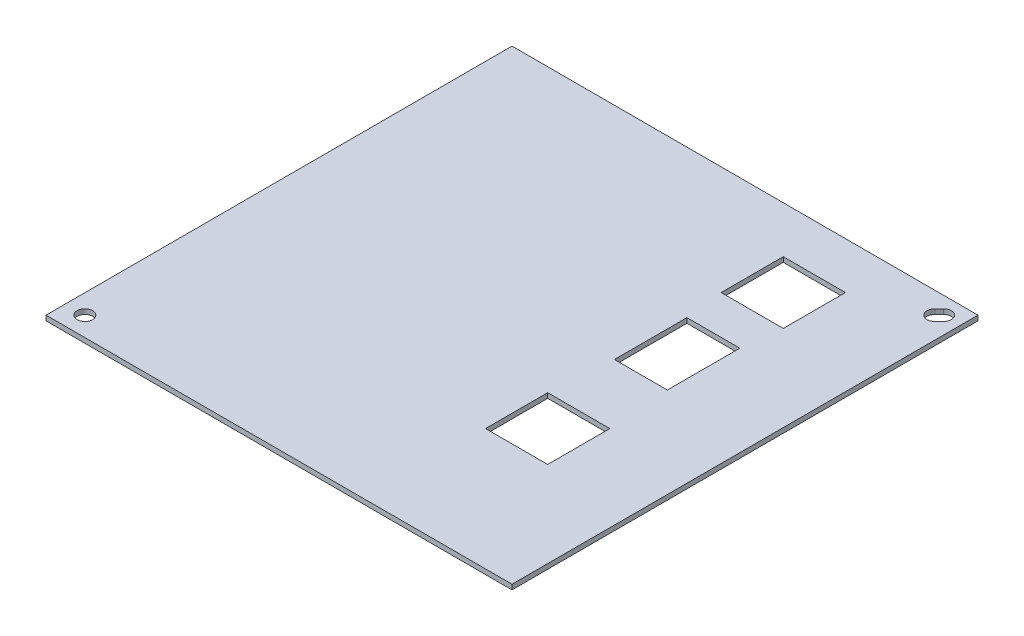
SolidWorks part; units mm, degrees
material "Acrylic (Medium-high impact)"
ref_plane "Front Plane" through (0, 0, 0) normal (0, 0, 1) x (1, 0, 0)
ref_plane "Top Plane" through (0, 0, 0) normal (0, 1, 0) x (1, 0, 0)
ref_plane "Right Plane" through (0, 0, 0) normal (1, 0, 0) x (0, 0, -1)
sketch "Sketch1" plane through (0, 0, 0) normal (0, 1, 0) x (1, 0, 0)
  line L1 (-150, -150) -> (150, -150)
  line L2 (-150, -150) -> (-150, 150)
  line L3 (-150, 150) -> (150, 150)
  line L4 (150, -150) -> (150, 150)
  line L5 (-150, -150) -> (150, 150) construction
  line L6 (-150, 150) -> (150, -150) construction
  point P0 (0, 0)
  dimension "D1" = 300
  dimension "D2" = 300
extrude "Boss-Extrude1" add sketch "Sketch1" along normal blind 3.175
sketch "Sketch2" plane through (0, 3.175, 0) normal (0, 1, 0) x (1, 0, 0)
  line L0 (138.9142, 138.9142) -> (136.0858, 136.0858) construction
  line L1 (142.4497, 135.3787) -> (139.6213, 132.5503)
  line L2 (135.3787, 142.4497) -> (132.5503, 139.6213)
  line L3 (-150, 150) -> (-150, -150) construction
  line L4 (-150, -150) -> (150, -150) construction
  line L5 (150, -150) -> (150, 150) construction
  line L6 (150, 150) -> (-150, 150) construction
  circle A0 centre (-137.5, -137.5) radius 5
  arc A1 (142.4497, 135.3787) -> (135.3787, 142.4497) centre (138.9142, 138.9142) ccw
  arc A2 (132.5503, 139.6213) -> (139.6213, 132.5503) centre (136.0858, 136.0858) ccw
  point P4 (137.5, 137.5)
  dimension "D2" = 10
  dimension "D7" = 5
  dimension "D1" = 12.5
  dimension "D3" = 12.5
  dimension "D4" = 12.5
  dimension "D5" = 12.5
  dimension "D6" = 4
extrude "Cut-Extrude1" cut sketch "Sketch2" against normal through all
sketch "Sketch3" plane through (0, 3.175, 0) normal (0, 1, 0) x (1, 0, 0)
  line L1 (57.686, 8.2571) -> (91.746, 8.2571)
  line L2 (57.686, 8.2571) -> (57.686, 54.9271)
  line L3 (57.686, 54.9271) -> (91.746, 54.9271)
  line L4 (91.746, 8.2571) -> (91.746, 54.9271)
  line L5 (57.686, 8.2571) -> (91.746, 54.9271) construction
  line L6 (57.686, 54.9271) -> (91.746, 8.2571) construction
  point P0 (74.716, 31.5921)
  dimension "D1" = 46.67
  dimension "D2" = 34.06
extrude "Cut-Extrude2" cut sketch "Sketch3" against normal through all
sketch "Sketch4" plane through (0, 3.175, 0) normal (0, 1, 0) x (1, 0, 0)
  line L0 (74.716, -51.7429) -> (74.716, 99.9271) construction
  line L1 (54.716, -71.7429) -> (94.716, -71.7429)
  line L2 (54.716, -71.7429) -> (54.716, -31.7429)
  line L3 (54.716, -31.7429) -> (94.716, -31.7429)
  line L4 (94.716, -71.7429) -> (94.716, -31.7429)
  line L5 (54.716, -71.7429) -> (94.716, -31.7429) construction
  line L6 (54.716, -31.7429) -> (94.716, -71.7429) construction
  line L7 (54.716, 79.9271) -> (94.716, 79.9271)
  line L8 (54.716, 79.9271) -> (54.716, 119.9271)
  line L9 (54.716, 119.9271) -> (94.716, 119.9271)
  line L10 (94.716, 79.9271) -> (94.716, 119.9271)
  line L11 (54.716, 79.9271) -> (94.716, 119.9271) construction
  line L12 (54.716, 119.9271) -> (94.716, 79.9271) construction
  line L14 (57.686, 8.2571) -> (91.746, 8.2571) construction
  line L15 (91.746, 54.9271) -> (57.686, 54.9271) construction
  point P0 (74.716, -51.7429)
  point P5 (74.716, 99.9271)
  point P14 (74.716, 8.2571)
  dimension "D1" = 40
  dimension "D2" = 40
  dimension "D3" = 25
  dimension "D4" = 40
extrude "Cut-Extrude3" cut sketch "Sketch4" against normal through all
